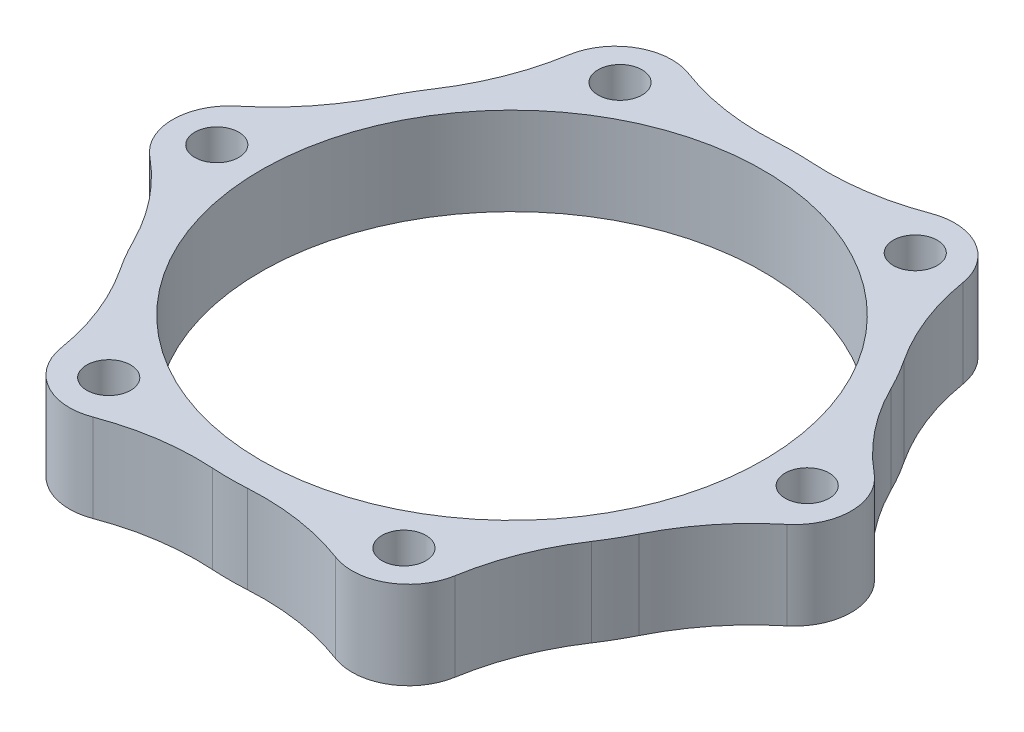
SolidWorks part; units mm, degrees
ref_plane "Front Plane" through (0, 0, 0) normal (0, 0, 1) x (1, 0, 0)
ref_plane "Top Plane" through (0, 0, 0) normal (0, 1, 0) x (1, 0, 0)
ref_plane "Right Plane" through (0, 0, 0) normal (1, 0, 0) x (0, 0, -1)
sketch "Sketch1" plane through (0, 0, 0) normal (0, 1, 0) x (1, 0, 0)
  circle A0 centre (0, 0) radius 28.575
  circle A1 centre (0, 0) radius 25.4
  circle A3 centre (0, 0) radius 25.4 construction
  dimension "D1" = 3.175
extrude "Boss-Extrude1" add sketch "Sketch1" along normal up to surface (8.89 mm away)
sketch "Sketch2" plane through (0, 8.89, 0) normal (0, 1, 0) x (1, 0, 0)
  line L0 (0, 0) -> (-28.575, 0) construction
  arc A0 (-28.0035, 5.6864) -> (-28.0035, -5.6864) centre (-28.575, 0) ccw
  circle A1 centre (0, 0) radius 28.575 construction
  arc A4 (-28.0035, 5.6864) -> (-28.0035, -5.6864) centre (0, 0) ccw
  dimension "D1" = 11.43
extrude "Boss-Extrude2" add sketch "Sketch2" against normal up to surface (8.89 mm away) contours A0 A4 up to face at (0, 0, 28.575)
fillet "Fillet1" radius 25.4 2 edges at (-28.0035, 4.445, -5.6864) (-28.0035, 4.445, 5.6864)
pattern_circular "CirPattern1" count 6 over 360 about axis through (0, 8.89, 0) along (0, 1, 0) of "Boss-Extrude2", "Fillet1"
sketch "Sketch3" plane through (0, 8.89, 0) normal (0, 1, 0) x (1, 0, 0)
  line L0 (-34.29, 0) -> (-25.4, 0) construction
  circle A0 centre (-29.845, 0) radius 2.2225
  arc A1 (-32.2023, 4.4163) -> (-32.2023, -4.4163) centre (-28.575, 0) ccw construction
  circle A2 centre (0, 0) radius 25.4 construction
  dimension "D1" = 4.445
extrude "Cut-Extrude1" cut sketch "Sketch3" against normal through all both and the other way through all
pattern_circular "CirPattern2" count 6 over 360 about axis through (0, 89.7123, 0) along (0, -1, 0) of "Cut-Extrude1"
